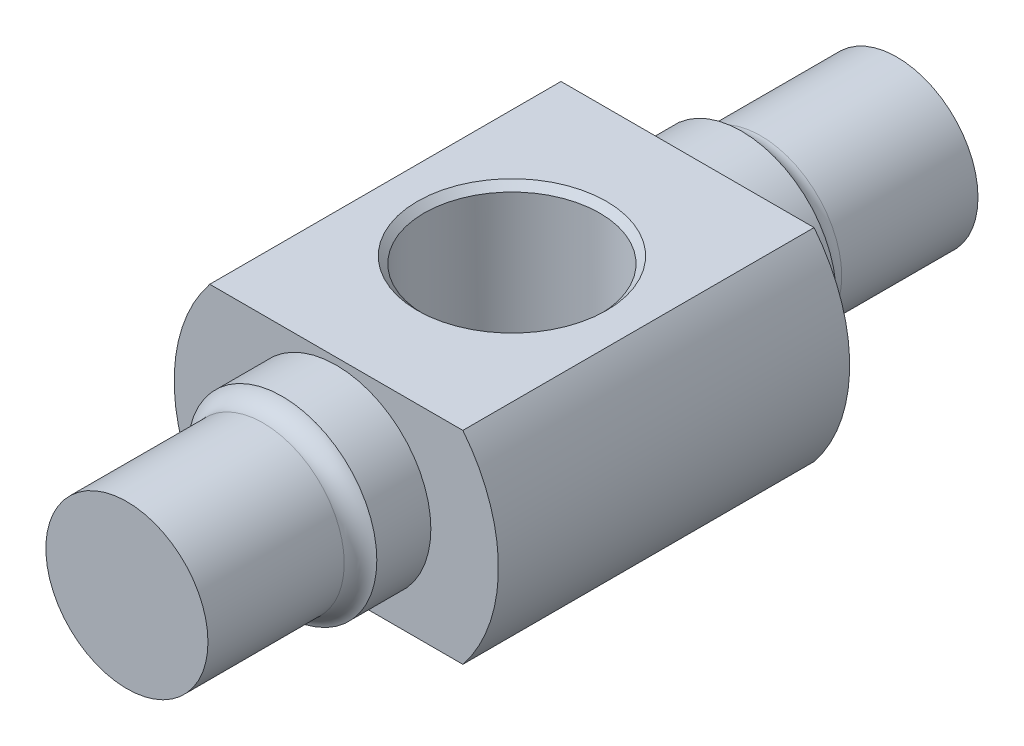
SolidWorks part; units mm, degrees
ref_plane "Piano frontale" through (0, 0, 0) normal (0, 0, 1) x (1, 0, 0)
ref_plane "Piano superiore" through (0, 0, 0) normal (0, 1, 0) x (1, 0, 0)
ref_plane "Piano destro" through (0, 0, 0) normal (1, 0, 0) x (0, 0, -1)
sketch "Schizzo2" plane through (0, 0, 0) normal (0, 0, 1) x (1, 0, 0)
  circle A0 centre (0, 0) radius 6
  dimension "D1" = 12
extrude "Estrusione-Estrusione1" add sketch "Schizzo2" along normal blind 11.5
cosmetic thread "Filettatura cosmetica2" parameters "D2"=10.072
sketch "Schizzo3" plane through (0, 0, 11.5) normal (0, 0, 1) x (1, 0, 0)
  circle A0 centre (0, 0) radius 7
  dimension "D1" = 14
extrude "Estrusione-Estrusione2" add sketch "Schizzo3" along normal blind 4
sketch "Schizzo4" plane through (0, 0, 15.5) normal (0, 0, 1) x (1, 0, 0)
  line L0 (-9.3675, 7.5) -> (9.3675, 7.5)
  line L5 (-9.3675, -7.5) -> (9.3675, -7.5)
  arc A0 (-9.3675, 7.5) -> (-9.3675, -7.5) centre (0, 0) ccw
  arc A2 (9.3675, -7.5) -> (9.3675, 7.5) centre (0, 0) ccw
  point P0 (0, 0)
  point P10 (-0.6595, -9.0151)
  dimension "D1" = 24
  dimension "D2" = 7.5
  dimension "D3" = 7.5
extrude "Estrusione-Estrusione3" add sketch "Schizzo4" along normal blind 26
ref_plane "Piano1" through (0, 0, 28.5) normal (0, 0, 1) x (1, 0, 0)
mirror "Specchia1" about plane through (0, 0, 28.5) normal (0, 0, 1) of "Estrusione-Estrusione1", "Estrusione-Estrusione2"
mirror "Specchia2" about plane through (0, 0, 28.5) normal (0, 0, 1) of "Estrusione-Estrusione1"
cosmetic thread "Filettatura cosmetica1" parameters "D2"=10.072
cosmetic thread "Filettatura cosmetica3" parameters "D2"=10.072
fillet "Raccordo2" radius 1.5 2 edges at (6, 0, 45.5) (6, 0, 11.5)
sketch "Schizzo6" plane through (0, 7.5, 0) normal (0, 1, 0) x (1, 0, 0)
  line L1 (-9.3675, -41.5) -> (-9.3675, -15.5) construction
  circle A0 centre (0, -28.5) radius 6.5
  point P5 (0, -28.5)
  point P6 (-2.5929, -28.5)
  point P7 (0, 0)
  point P9 (0, 0)
  point P10 (0, 0)
  point P11 (0, 0)
  point P12 (0, -27.8321)
  point P13 (0, -23.9034)
  point P14 (0, 0)
  point P17 (-9.3675, -28.5)
  dimension "D1" = 13
extrude "Taglio-Estrusione2" cut sketch "Schizzo6" against normal through all
chamfer "Smusso2" distance 0.5 angle 45 2 edges at (0, -7.5, 35) (0, 7.5, 35)
